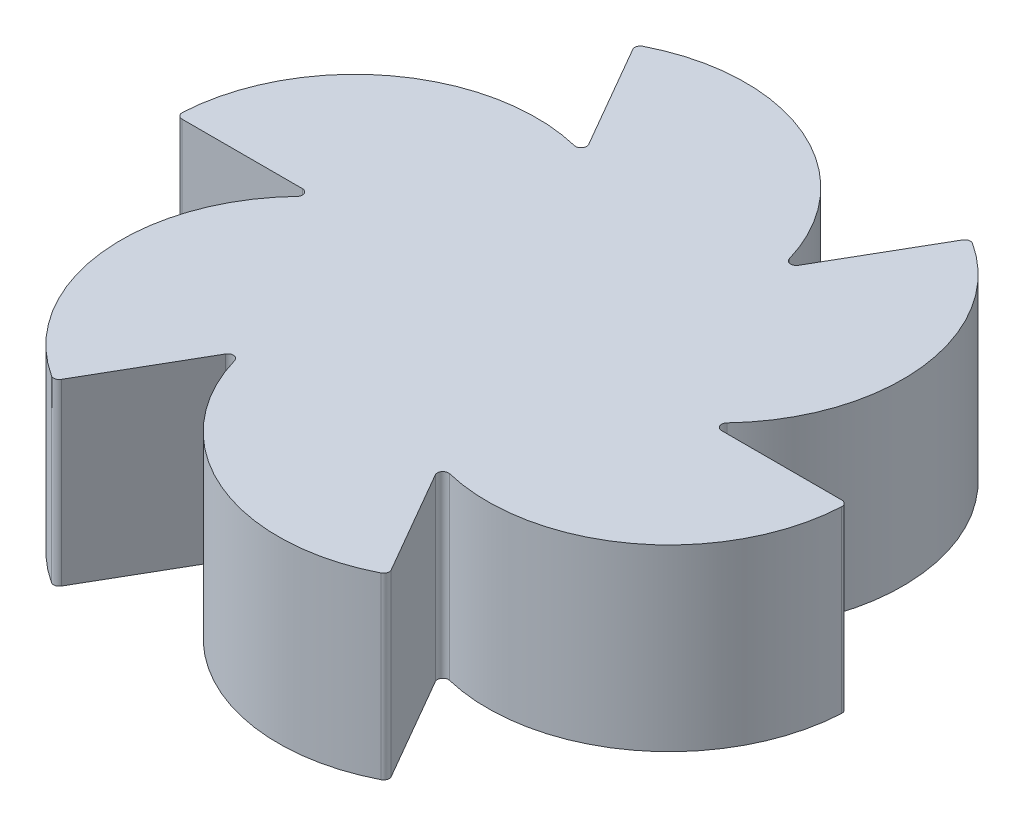
SolidWorks part; units mm, degrees
ref_plane "Front Plane" through (0, 0, 0) normal (0, 0, 1) x (1, 0, 0)
ref_plane "Top Plane" through (0, 0, 0) normal (0, 1, 0) x (1, 0, 0)
ref_plane "Right Plane" through (0, 0, 0) normal (1, 0, 0) x (0, 0, -1)
sketch "Sketch1" plane through (0, 0, 0) normal (0, 1, 0) x (1, 0, 0)
  line L4 (-12, 0) -> (-7, 0)
  line L5 (-6, 10.3923) -> (-3.5, 6.0622)
  line L9 (6, 10.3923) -> (3.5, 6.0622)
  line L10 (12, 0) -> (7, 0)
  line L11 (6, -10.3923) -> (3.5, -6.0622)
  line L12 (-6, -10.3923) -> (-3.5, -6.0622)
  arc A12 (-12, 0) -> (-3.5, 6.0622) centre (-5.5011, -0.1221) cw
  arc A13 (-6, 10.3923) -> (3.5, 6.0622) centre (-2.8563, 4.7031) cw
  arc A14 (6, 10.3923) -> (7, 0) centre (2.6448, 4.8252) cw
  arc A15 (12, 0) -> (3.5, -6.0622) centre (5.5011, 0.1221) cw
  arc A16 (6, -10.3923) -> (-3.5, -6.0622) centre (2.8563, -4.7031) cw
  arc A17 (-6, -10.3923) -> (-7, 0) centre (-2.6448, -4.8252) cw
  point P27 (0, 0)
  dimension "D1" = 24
  dimension "D2" = 6
  dimension "D3" = 6.5
  dimension "D4" = 5
extrude "Boss-Extrude1" add sketch "Sketch1" along normal blind 1.4 contours A17 L12 A16 L11 A15 L10 A14 L9 A13 L5 A12 L4
fillet "Fillet1" radius 0.2 12 edges at (7, 0.7, 0) (12, 0.7, 0) (3.5, 0.7, 6.0622) (6, 0.7, 10.3923) (-3.5, 0.7, 6.0622) (-6, 0.7, 10.3923) (-7, 0.7, 0) (-12, 0.7, 0) (-3.5, 0.7, -6.0622) (-6, 0.7, -10.3923) (3.5, 0.7, -6.0622) (6, 0.7, -10.3923)
ref_axis "Axis1" through (0, 2.52, 0) along (0, -1, 0)
sketch "Sketch2" plane through (0, 0, 0) normal (0, -1, 0) x (1, 0, 0)
  line L1 (2.2517, 0) -> (1.1258, 1.95)
  line L2 (1.1258, 1.95) -> (-1.1258, 1.95)
  line L3 (-1.1258, 1.95) -> (-2.2517, 0)
  line L4 (-2.2517, 0) -> (-1.1258, -1.95)
  line L5 (-1.1258, -1.95) -> (1.1258, -1.95)
  line L6 (1.1258, -1.95) -> (2.2517, 0)
  line L12 (7.4923, 0) -> (11.7929, 0)
  line L13 (3.7461, 6.4885) -> (5.8965, 10.213)
  line L17 (-3.7461, 6.4885) -> (-5.8965, 10.213)
  line L18 (-7.4923, 0) -> (-11.7929, 0)
  line L19 (-3.7461, -6.4885) -> (-5.8965, -10.213)
  line L20 (3.7461, -6.4885) -> (5.8965, -10.213)
  line L21 (7.4923, 0) -> (11.7929, 0)
  line L22 (3.7461, 6.4885) -> (5.8965, 10.213)
  line L23 (-3.7461, 6.4885) -> (-5.8965, 10.213)
  line L24 (-7.4923, 0) -> (-11.7929, 0)
  line L25 (-3.7461, -6.4885) -> (-5.8965, -10.213)
  line L26 (3.7461, -6.4885) -> (5.8965, -10.213)
  circle A0 centre (0, 0) radius 1.95 construction
  circle A1 centre (0, 0) radius 4.3
  arc A26 (11.7929, 0) -> (11.9926, 0.2102) centre (11.7929, 0.2) ccw
  arc A28 (11.9926, 0.2102) -> (3.9666, 6.1941) centre (5.5011, -0.1221) ccw
  arc A30 (11.7929, 0) -> (11.9926, 0.2102) centre (11.7929, 0.2) ccw
  arc A32 (3.7461, 6.4885) -> (3.9666, 6.1941) centre (3.9193, 6.3885) ccw
  arc A34 (5.8143, 10.491) -> (-3.381, 6.5322) centre (2.8563, 4.7031) ccw
  arc A36 (3.7461, 6.4885) -> (3.9666, 6.1941) centre (3.9193, 6.3885) ccw
  arc A38 (-6.1784, 10.2808) -> (-7.3476, 0.3381) centre (-2.6448, 4.8252) ccw
  arc A39 (5.8965, 10.213) -> (5.8143, 10.491) centre (5.7232, 10.313) ccw
  arc A40 (5.8965, 10.213) -> (5.8143, 10.491) centre (5.7232, 10.313) ccw
  arc A41 (-11.9926, -0.2102) -> (-3.9666, -6.1941) centre (-5.5011, 0.1221) ccw
  arc A42 (-3.7461, 6.4885) -> (-3.381, 6.5322) centre (-3.5729, 6.5885) ccw
  arc A43 (-3.7461, 6.4885) -> (-3.381, 6.5322) centre (-3.5729, 6.5885) ccw
  arc A44 (-5.8143, -10.491) -> (3.381, -6.5322) centre (-2.8563, -4.7031) ccw
  arc A45 (-5.8965, 10.213) -> (-6.1784, 10.2808) centre (-6.0697, 10.113) ccw
  arc A46 (-5.8965, 10.213) -> (-6.1784, 10.2808) centre (-6.0697, 10.113) ccw
  arc A47 (6.1784, -10.2808) -> (7.3476, -0.3381) centre (2.6448, -4.8252) ccw
  arc A48 (-7.4923, 0) -> (-7.3476, 0.3381) centre (-7.4923, 0.2) ccw
  arc A50 (11.9926, 0.2102) -> (3.9666, 6.1941) centre (5.5011, -0.1221) ccw
  arc A53 (5.8143, 10.491) -> (-3.381, 6.5322) centre (2.8563, 4.7031) ccw
  arc A56 (-6.1784, 10.2808) -> (-7.3476, 0.3381) centre (-2.6448, 4.8252) ccw
  arc A59 (-11.9926, -0.2102) -> (-3.9666, -6.1941) centre (-5.5011, 0.1221) ccw
  arc A62 (-5.8143, -10.491) -> (3.381, -6.5322) centre (-2.8563, -4.7031) ccw
  arc A65 (6.1784, -10.2808) -> (7.3476, -0.3381) centre (2.6448, -4.8252) ccw
  arc A66 (-7.4923, 0) -> (-7.3476, 0.3381) centre (-7.4923, 0.2) ccw
  arc A67 (-11.7929, 0) -> (-11.9926, -0.2102) centre (-11.7929, -0.2) ccw
  arc A68 (-11.7929, 0) -> (-11.9926, -0.2102) centre (-11.7929, -0.2) ccw
  arc A69 (-3.7461, -6.4885) -> (-3.9666, -6.1941) centre (-3.9193, -6.3885) ccw
  arc A70 (-3.7461, -6.4885) -> (-3.9666, -6.1941) centre (-3.9193, -6.3885) ccw
  arc A71 (-5.8965, -10.213) -> (-5.8143, -10.491) centre (-5.7232, -10.313) ccw
  arc A72 (-5.8965, -10.213) -> (-5.8143, -10.491) centre (-5.7232, -10.313) ccw
  arc A73 (3.7461, -6.4885) -> (3.381, -6.5322) centre (3.5729, -6.5885) ccw
  arc A74 (3.7461, -6.4885) -> (3.381, -6.5322) centre (3.5729, -6.5885) ccw
  arc A75 (5.8965, -10.213) -> (6.1784, -10.2808) centre (6.0697, -10.113) ccw
  arc A76 (5.8965, -10.213) -> (6.1784, -10.2808) centre (6.0697, -10.113) ccw
  arc A77 (7.4923, 0) -> (7.3476, -0.3381) centre (7.4923, -0.2) ccw
  arc A78 (7.4923, 0) -> (7.3476, -0.3381) centre (7.4923, -0.2) ccw
  dimension "D2" = 8.6
  dimension "D1" = 3.9
  dimension "D3" = 0
extrude "Boss-Extrude2" add sketch "Sketch2" along normal blind 2.5 contours A78 L21 A30 A50 A36 L22 A40 A53 A43 L23 A46 A56 A66 L24 A68 A59 A70 L25 A72 A62 A74 L26 A76 A65 A1 | L5 L6 L1 L2 L3 L4 region at (7.0066, 0, 0.0079)
extrude "Boss-Extrude3" add sketch "Sketch2<3>" along normal blind 5 contours A1 region at (7.0066, 0, 0.0079)
sketch "Sketch2<3>" plane through (0, 0, 0) normal (0, -1, 0) x (1, 0, 0) same geometry as "Sketch2"
